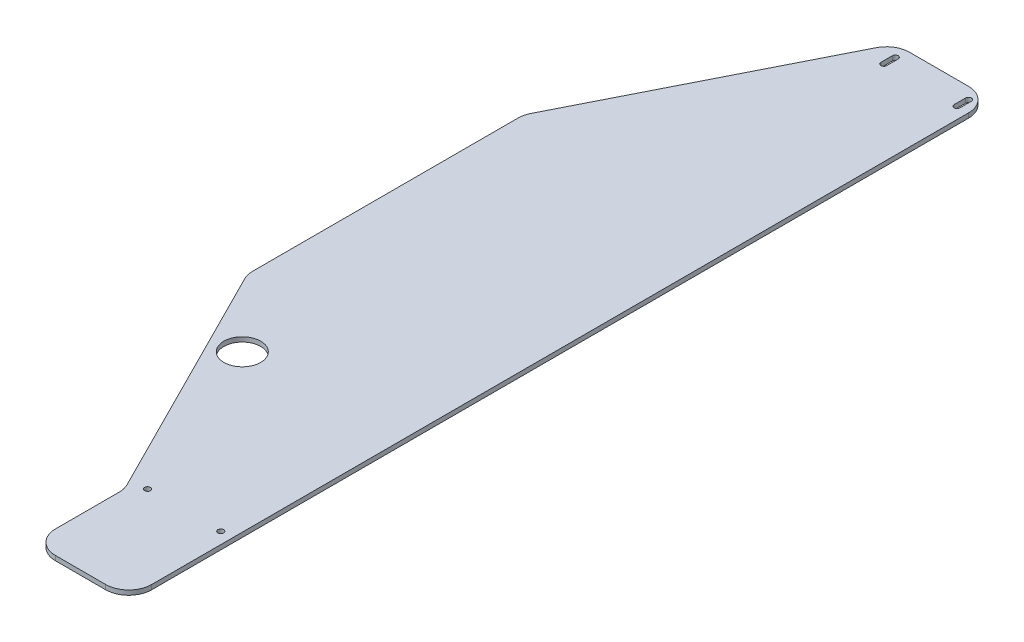
SolidWorks part; units mm, degrees
ref_plane "Front Plane" through (0, 0, 0) normal (0, 0, 1) x (1, 0, 0)
ref_plane "Top Plane" through (0, 0, 0) normal (0, 1, 0) x (1, 0, 0)
ref_plane "Right Plane" through (0, 0, 0) normal (1, 0, 0) x (0, 0, -1)
sketch "Sketch1" plane through (0, 0, 0) normal (0, 1, 0) x (1, 0, 0)
  line L0 (5, 329.76) -> (0, 334.76) construction
  line L1 (0, 0) -> (41.8, 0)
  line L2 (0, 0) -> (0, 334.76) construction
  line L3 (0, 334.76) -> (41.8, 334.76)
  line L4 (41.8, 0) -> (41.8, 334.76)
  line L5 (5, 327.26) -> (36.8, 327.26) construction
  line L6 (5, 327.26) -> (5, 5) construction
  line L7 (5, 5) -> (36.8, 5) construction
  line L8 (36.8, 327.26) -> (36.8, 5) construction
  line L9 (36.8, 329.76) -> (41.8, 334.76) construction
  line L10 (36.8, 5) -> (41.8, 0) construction
  line L11 (5, 5) -> (0, 0) construction
  line L12 (5, 329.76) -> (5, 324.76) construction
  line L13 (6.25, 329.76) -> (6.25, 324.76)
  line L14 (3.75, 329.76) -> (3.75, 324.76)
  line L15 (36.8, 329.76) -> (36.8, 324.76) construction
  line L16 (38.05, 329.76) -> (38.05, 324.76)
  line L17 (35.55, 329.76) -> (35.55, 324.76)
  line L18 (0, 334.76) -> (-54.1, 227.38)
  line L19 (-54.1, 227.38) -> (-54.1, 107.38)
  line L20 (-54.1, 107.38) -> (0, 0)
  line L25 (0, 0) -> (41.8, 0)
  line L26 (0, 0) -> (0, -40)
  line L27 (0, -40) -> (41.8, -40)
  line L28 (41.8, 0) -> (41.8, -40)
  circle A0 centre (5, 5) radius 1.25
  circle A1 centre (36.8, 5) radius 1.25
  arc A4 (6.25, 329.76) -> (3.75, 329.76) centre (5, 329.76) ccw
  arc A5 (3.75, 324.76) -> (6.25, 324.76) centre (5, 324.76) ccw
  arc A6 (38.05, 329.76) -> (35.55, 329.76) centre (36.8, 329.76) ccw
  arc A7 (35.55, 324.76) -> (38.05, 324.76) centre (36.8, 324.76) ccw
  point P13 (5, 327.26)
  point P19 (36.8, 327.26)
  dimension "D3" = 2.5
  dimension "D1" = 322.26
  dimension "D2" = 31.8
  dimension "D4" = 5
  dimension "D5" = 5
  dimension "D6" = 5
  dimension "D8" = 120
  dimension "D9" = 40
extrude "Boss-Extrude1" add sketch "Sketch1" along normal blind 2 contours L3 L18 L19 L20 L1 A7 L17 A6 L16 A5 L14 A4 L13 A1 A0 | L28 L1 L26 L27 region at (0.4248, 0, -167.2287) region at (20.9, 0, 20)
sketch "Sketch4" plane through (0, 2, 0) normal (0, 1, 0) x (1, 0, 0)
  circle A0 centre (-26.0566, 77.1883) radius 8
  point P2 (60.1629, 59.9288)
  point P3 (55.6617, 52.6541)
  point P4 (17.4548, 44.014)
  point P5 (-26.0566, 77.1883)
  dimension "D1" = 16
extrude "Cut-Extrude3" cut sketch "Sketch4" against normal through all
fillet "Fillet1" radius 10 7 edges at (41.8, 1, -334.76) (0, 1, -334.76) (-54.1, 1, -227.38) (-54.1, 1, -107.38) (0, 1, 0) (0, 1, 40) (41.8, 1, 40)
